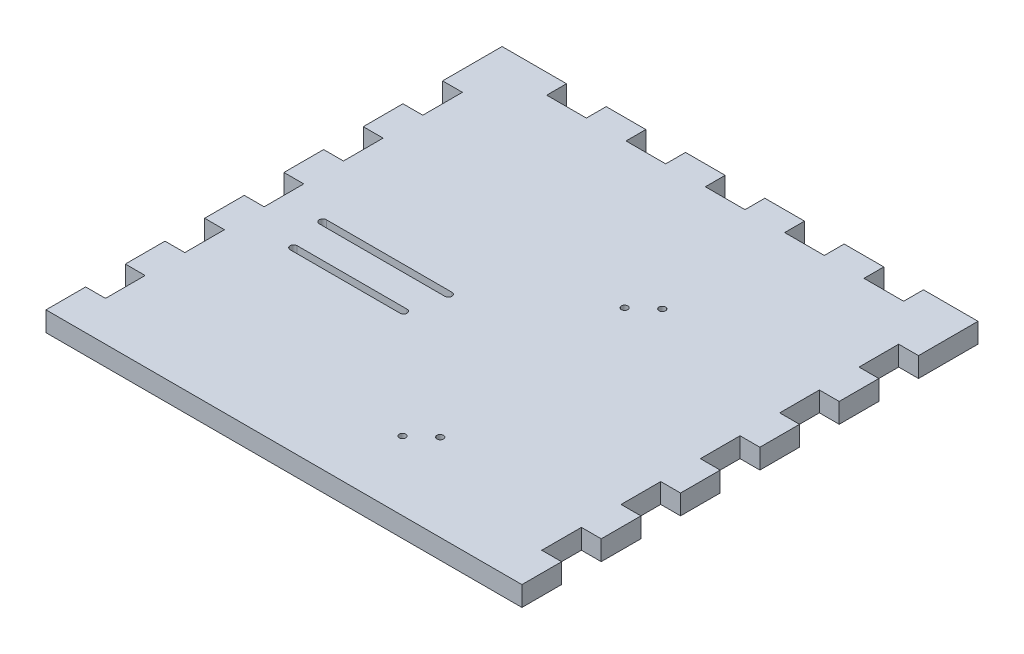
SolidWorks part; units mm, degrees
ref_plane "Front Plane" through (0, 0, 0) normal (0, 0, 1) x (1, 0, 0)
ref_plane "Top Plane" through (0, 0, 0) normal (0, 1, 0) x (1, 0, 0)
ref_plane "Right Plane" through (0, 0, 0) normal (1, 0, 0) x (0, 0, -1)
sketch "Sketch1" plane through (0, 0, 0) normal (0, 1, 0) x (1, 0, 0)
  line L1 (-139.7, -139.7) -> (139.7, -139.7)
  line L2 (-139.7, -139.7) -> (-139.7, 139.7)
  line L3 (-139.7, 139.7) -> (139.7, 139.7)
  line L4 (139.7, -139.7) -> (139.7, 139.7)
  line L5 (-139.7, -139.7) -> (139.7, 139.7) construction
  line L6 (-139.7, 139.7) -> (139.7, -139.7) construction
  point P0 (0, 0)
  dimension "D1" = 279.4
  dimension "D2" = 279.4
extrude "Boss-Extrude1" add sketch "Sketch1" along normal blind 12.7
sketch "Sketch2" plane through (139.7, 0, 0) normal (1, 0, 0) x (0, 0, -1)
  line L0 (-139.7, 12.7) -> (139.7, 12.7) construction
  line L1 (-139.7, 0) -> (-114.3, 0)
  line L2 (-139.7, 0) -> (-139.7, 12.7)
  line L3 (-139.7, 12.7) -> (-114.3, 12.7)
  line L4 (-114.3, 0) -> (-114.3, 12.7)
  dimension "D1" = 25.4
extrude "Boss-Extrude2" add sketch "Sketch2" along normal blind 12.7
pattern_linear "LPattern1" count 6 spacing 50.8 along (0, 0, -1) of "Boss-Extrude2"
mirror "Mirror1" about plane through (0, 0, 0) normal (1, 0, 0) of "LPattern1"
sketch "Sketch3" plane through (0, 0, -139.7) normal (0, 0, -1) x (-1, 0, 0)
  line L0 (-152.4, 12.7) -> (152.4, 12.7) construction
  line L1 (-142.875, 12.7) -> (-117.475, 12.7)
  line L2 (-142.875, 12.7) -> (-142.875, 0)
  line L3 (-142.875, 0) -> (-117.475, 0)
  line L4 (-117.475, 12.7) -> (-117.475, 0)
  line L5 (-152.4, 0) -> (152.4, 0) construction
  line L6 (-152.4, 0) -> (-152.4, 12.7) construction
  dimension "D1" = 9.525
  dimension "D2" = 25.4
extrude "Boss-Extrude3" add sketch "Sketch3" along normal blind 12.7
pattern_linear "LPattern2" count 6 spacing 50.8 along (-1, 0, 0) of "Boss-Extrude3"
sketch "Sketch5" plane through (0, 0, -139.7) normal (0, 0, -1) x (-1, 0, 0)
  line L11 (160.655, 0) -> (-160.655, 0) construction
  line L12 (-152.4, 12.7) -> (-127, 12.7)
  line L13 (-152.4, 12.7) -> (-152.4, 0)
  line L14 (-152.4, 0) -> (-127, 0)
  line L15 (-127, 12.7) -> (-127, 0)
  dimension "D1" = 25.4
extrude "Boss-Extrude4" add sketch "Sketch5" along normal blind 12.7
mirror "Mirror2" about plane through (0, 0, 0) normal (1, 0, 0) of "Boss-Extrude4"
sketch "Sketch6" plane through (0, 0, 0) normal (0, -1, 0) x (1, 0, 0)
  circle A0 centre (44.45, -58.1456) radius 2.1 construction
  circle A1 centre (44.45, -58.1456) radius 2.1
  circle A2 centre (31.75, -46.7156) radius 2.1 construction
  circle A3 centre (31.75, -46.7156) radius 2.1
  circle A4 centre (31.75, 95.5244) radius 2.1 construction
  circle A5 centre (31.75, 95.5244) radius 2.1
  circle A6 centre (44.45, 84.0944) radius 2.1 construction
  circle A7 centre (44.45, 84.0944) radius 2.1
extrude "Cut-Extrude1" cut sketch "Sketch6" against normal through all
sketch "Sketch7" plane through (0, 0, 0) normal (0, -1, 0) x (1, 0, 0)
  circle A0 centre (31.75, 95.5244) radius 4.318
  circle A1 centre (31.75, 95.5244) radius 2.1 construction
  circle A2 centre (44.45, 84.0944) radius 4.318
  circle A3 centre (31.75, -46.7156) radius 4.318
  circle A4 centre (44.45, -58.1456) radius 4.318
  dimension "D1" = 8.636
  dimension "D2" = 8.636
  dimension "D3" = 8.636
  dimension "D4" = 8.636
extrude "Cut-Extrude2" cut sketch "Sketch7" against normal blind 6.35
sketch "Sketch8" plane through (0, 12.7, 0) normal (0, 1, 0) x (1, 0, 0)
  circle A0 centre (-49.9203, -25.9489) radius 2.2225 construction
  circle A1 centre (-49.9203, -25.9489) radius 2.2225
  circle A2 centre (-44.9203, -2.2189) radius 2.2225 construction
  circle A3 centre (-44.9203, -2.2189) radius 2.2225
  circle A4 centre (-94.9203, -25.9489) radius 2.2225 construction
  circle A5 centre (-94.9203, -25.9489) radius 2.2225
  circle A6 centre (-99.9203, -2.2189) radius 2.2225 construction
  circle A7 centre (-99.9203, -2.2189) radius 2.2225
extrude "Cut-Extrude3" cut sketch "Sketch8" against normal through all
sketch "Sketch9" plane through (0, 0, 0) normal (0, -1, 0) x (1, 0, 0)
  circle A0 centre (-94.9203, 25.9489) radius 6.35
  circle A1 centre (-99.9203, 2.2189) radius 6.35
  circle A2 centre (-44.9203, 2.2189) radius 6.35
  circle A3 centre (-49.9203, 25.9489) radius 6.35
  dimension "D1" = 12.7
  dimension "D2" = 12.7
  dimension "D3" = 12.7
  dimension "D4" = 12.7
extrude "Cut-Extrude4" cut sketch "Sketch9" against normal blind 6.35
sketch "Sketch10" plane through (0, 0, 0) normal (0, -1, 0) x (1, 0, 0)
  line L0 (-94.9203, 25.9489) -> (-49.9203, 25.9489) construction
  line L1 (-49.9203, 25.9489) -> (-37.1427, 25.9489) construction
  line L2 (-94.9203, 25.9489) -> (-107.5477, 25.9489) construction
  line L3 (-44.9203, 2.2189) -> (-99.9203, 2.2189) construction
  line L4 (-99.9203, 2.2189) -> (-112.6283, 2.2189) construction
  line L5 (-44.9203, 2.2189) -> (-32.1847, 2.2189) construction
  line L6 (-107.5477, 25.9489) -> (-37.1427, 25.9489) construction
  line L7 (-107.5477, 32.3162) -> (-37.1427, 32.3162)
  line L8 (-107.5477, 19.5816) -> (-37.1427, 19.5816)
  line L9 (-112.6283, 2.2189) -> (-32.1847, 2.2189) construction
  line L10 (-112.6283, 8.6979) -> (-32.1847, 8.6979)
  line L11 (-112.6283, -4.2601) -> (-32.1847, -4.2601)
  line L12 (-112.6283, 2.2189) -> (-32.1847, 2.2189) construction
  line L13 (-112.6283, 4.4839) -> (-32.1847, 4.4839)
  line L14 (-112.6283, -0.0461) -> (-32.1847, -0.0461)
  line L15 (-107.5477, 25.9489) -> (-37.1427, 25.9489) construction
  line L16 (-107.5477, 28.2001) -> (-37.1427, 28.2001)
  line L17 (-107.5477, 23.6977) -> (-37.1427, 23.6977)
  arc A0 (-107.5477, 32.3162) -> (-107.5477, 19.5816) centre (-107.5477, 25.9489) ccw
  arc A1 (-37.1427, 19.5816) -> (-37.1427, 32.3162) centre (-37.1427, 25.9489) ccw
  arc A2 (-112.6283, 8.6979) -> (-112.6283, -4.2601) centre (-112.6283, 2.2189) ccw
  arc A3 (-32.1847, -4.2601) -> (-32.1847, 8.6979) centre (-32.1847, 2.2189) ccw
  arc A4 (-112.6283, 4.4839) -> (-112.6283, -0.0461) centre (-112.6283, 2.2189) ccw
  arc A5 (-32.1847, -0.0461) -> (-32.1847, 4.4839) centre (-32.1847, 2.2189) ccw
  arc A6 (-107.5477, 28.2001) -> (-107.5477, 23.6977) centre (-107.5477, 25.9489) ccw
  arc A7 (-37.1427, 23.6977) -> (-37.1427, 28.2001) centre (-37.1427, 25.9489) ccw
  point P4 (-72.3452, 25.9489)
  point P17 (-72.4065, 2.2189)
  point P22 (-72.4065, 2.2189)
  point P29 (-72.3452, 25.9489)
  point P36 (0, 0)
extrude "Cut-Extrude5" cut sketch "Sketch10" against normal through all contours L16 A7 L17 A6 | L14 A5 L13 A4
sketch "Sketch12" plane through (0, 0, 0) normal (0, -1, 0) x (1, 0, 0)
  line L0 (-107.5477, 25.9489) -> (-37.7917, 25.9489) construction
  line L1 (-107.5477, 32.4644) -> (-37.7917, 32.4644)
  line L2 (-107.5477, 19.4334) -> (-37.7917, 19.4334)
  arc A0 (-107.5477, 32.4644) -> (-107.5477, 19.4334) centre (-107.5477, 25.9489) ccw
  arc A1 (-37.7917, 19.4334) -> (-37.7917, 32.4644) centre (-37.7917, 25.9489) ccw
  point P3 (-72.6697, 25.9489)
extrude "Cut-Extrude6" cut sketch "Sketch12" against normal blind 6.35
extrude "Cut-Extrude7" cut sketch "Sketch10<3>" against normal blind 6.35
sketch "Sketch10<3>" plane through (0, 0, 0) normal (0, -1, 0) x (1, 0, 0) same geometry as "Sketch10"
